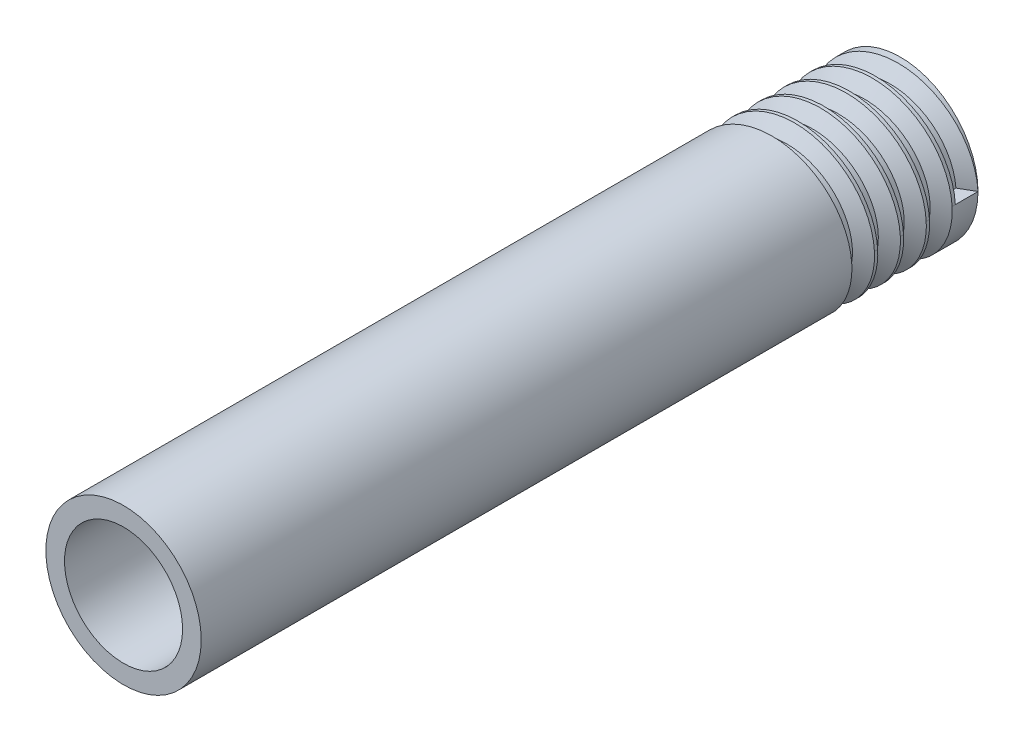
SolidWorks part; units mm, degrees
ref_plane "Front Plane" through (0, 0, 0) normal (0, 0, 1) x (1, 0, 0)
ref_plane "Top Plane" through (0, 0, 0) normal (0, 1, 0) x (1, 0, 0)
ref_plane "Right Plane" through (0, 0, 0) normal (1, 0, 0) x (0, 0, -1)
sketch "Sketch1" plane through (0, 0, 0) normal (0, 0, 1) x (1, 0, 0)
  circle A0 centre (0, 0) radius 6.35
  circle A1 centre (0, 0) radius 4.826
extrude "Boss-Extrude1" add sketch "Sketch1" along normal blind 63.5 contours A0 | A1
thread "Thread1" pitch 2.1167 method cut profile "Thread Profile1" start angle 0, offset 0, length 10, pitch 2.1167, diameter 12.7
ref_plane "Plane1" through (6.35, 0, 0) normal (0, -1, 0) x (1, 0, 0)
sketch "Thread Profile1" plane through (6.35, 0, 0) normal (0, -1, 0) x (1, 0, 0)
  line L0 (0, 0) -> (0, 2.1167) construction
  line L11 (0, 0) -> (0, 1.8521)
  line L12 (0, 1.8521) -> (-1.1457, 1.1906)
  line L13 (-1.1457, 1.1906) -> (-1.1457, 0.6615)
  line L15 (-1.1457, 0.6615) -> (0, 0)
  line L17 (-1.1457, 0.926) -> (0, 0.926) construction
  point P2 (0, 0)
  dimension "Pitch" = 2.1167
  dimension "Profile_Angle" = 60
  dimension "Profile_Land" = 0.5292
  dimension "Profile_Height" = 1.1457
